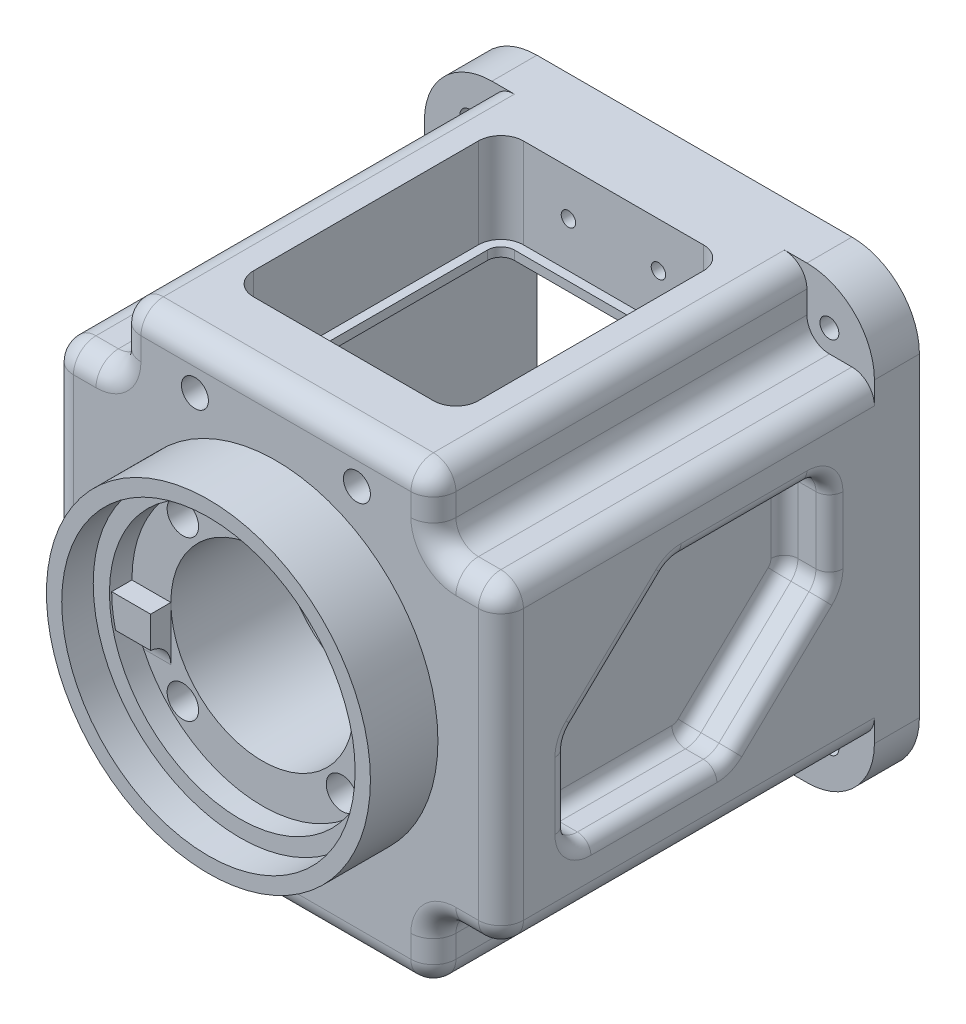
SolidWorks part; units mm, degrees
ref_plane "前视基准面" through (0, 0, 0) normal (0, 0, 1) x (1, 0, 0)
ref_plane "上视基准面" through (0, 0, 0) normal (0, 1, 0) x (1, 0, 0)
ref_plane "右视基准面" through (0, 0, 0) normal (1, 0, 0) x (0, 0, -1)
sketch "草图1" plane through (0, 0, 0) normal (0, 0, 1) x (1, 0, 0)
  line L1 (-50, 50) -> (50, 50)
  line L2 (-50, 50) -> (-50, -50)
  line L3 (-50, -50) -> (50, -50)
  line L4 (50, 50) -> (50, -50)
  line L5 (0, -50) -> (0, 50) construction
  line L6 (-50, 0) -> (50, 0) construction
  point P0 (0, 0)
  dimension "D1" = 100
  dimension "D2" = 100
extrude "凸台-拉伸1" add sketch "草图1" along normal blind 93
fillet "圆角1" radius 15 4 edges at (-50, -50, 46.5) (50, -50, 46.5) (50, 50, 46.5) (-50, 50, 46.5)
sketch "草图2" plane through (0, 0, 93) normal (0, 0, 1) x (1, 0, 0)
  line L0 (35, 50) -> (-35, 50) construction
  line L1 (-35, 50) -> (-50, 50)
  line L2 (-35, 50) -> (-35, 40)
  line L3 (-40, 35) -> (-50, 35)
  line L4 (-50, 50) -> (-50, 35)
  line L5 (-50, 35) -> (-50, -35) construction
  line L6 (50, 35) -> (40, 35)
  line L7 (50, 35) -> (50, 50)
  line L8 (50, 50) -> (35, 50)
  line L9 (35, 40) -> (35, 50)
  line L10 (35, -50) -> (35, -40)
  line L11 (35, -50) -> (50, -50)
  line L12 (50, -50) -> (50, -35)
  line L13 (40, -35) -> (50, -35)
  line L14 (-50, -35) -> (-40, -35)
  line L15 (-50, -35) -> (-50, -50)
  line L16 (-50, -50) -> (-35, -50)
  line L17 (-35, -40) -> (-35, -50)
  arc A0 (-35, 40) -> (-40, 35) centre (-40, 40) cw
  arc A1 (40, 35) -> (35, 40) centre (40, 40) cw
  arc A2 (35, -40) -> (40, -35) centre (40, -40) cw
  arc A3 (-40, -35) -> (-35, -40) centre (-40, -40) cw
  point P31 (0, 0)
  dimension "D3" = 5
  dimension "D1" = 15
  dimension "D2" = 15
  dimension "D4" = 4
extrude "切除-拉伸1" cut sketch "草图2" against normal offset from surface (83 mm away) 10 up to face at (0, 0, 0)
sketch "草图3" plane through (0, -50, 0) normal (0, -1, 0) x (1, 0, 0)
  line L1 (0, 46.5) -> (-87.2172, 46.5) construction
  line L4 (0, 46.5) -> (0, 0) construction
  line L5 (-35, 93) -> (35, 93) construction
  line L6 (-35, 0) -> (35, 0) construction
  circle A0 centre (0, 46.5) radius 25
  circle A1 centre (0, 46.5) radius 15
  dimension "D1" = 50
  dimension "D2" = 30
extrude "切除-拉伸2" cut sketch "草图3" against normal blind 7
sketch "草图4" plane through (0, -43, 0) normal (0, -1, 0) x (1, 0, 0)
  circle A0 centre (0, 46.5) radius 16
  circle A1 centre (0, 46.5) radius 24
  dimension "D1" = 48
  dimension "D2" = 32
extrude "切除-拉伸3" cut sketch "草图4" against normal blind 3
chamfer "倒角1" distance 1 angle 45 2 edges at (0, -50, 31.5) (0, -50, 21.5)
sketch "草图5" plane through (0, 0, 93) normal (0, 0, 1) x (1, 0, 0)
  circle A0 centre (0, 0) radius 36
  dimension "D1" = 72
extrude "凸台-拉伸2" add sketch "草图5" along normal blind 15
sketch "草图6" plane through (0, 0, 108) normal (0, 0, 1) x (1, 0, 0)
  circle A0 centre (0, 0) radius 32.6
  dimension "D2" = 65.2
extrude "切除-拉伸4" cut sketch "草图6" against normal blind 7
sketch "草图7" plane through (0, 0, 101) normal (0, 0, 1) x (1, 0, 0)
  circle A0 centre (0, 0) radius 29
  dimension "D1" = 58
extrude "切除-拉伸5" cut sketch "草图7" against normal blind 5
sketch "草图8" plane through (0, 0, 96) normal (0, 0, 1) x (1, 0, 0)
  line L0 (0, 0) -> (-51.1806, 0) construction
  line L1 (-17.6777, 17.6777) -> (0, 0) construction
  circle A0 centre (0, 0) radius 20.35
  circle A1 centre (-17.6777, 17.6777) radius 2.1
  circle A2 centre (17.6777, 17.6777) radius 2.1
  circle A3 centre (17.6777, -17.6777) radius 2.1
  circle A4 centre (-17.6777, -17.6777) radius 2.1
  point P15 (0, 0)
  dimension "D1" = 40.7
  dimension "D3" = 4.2
  dimension "D2" = 45
  dimension "D4" = 25
  dimension "D5" = 4
extrude "切除-拉伸6" cut sketch "草图8" against normal through all
sketch "草图9" plane through (0, 0, 96) normal (0, 0, 1) x (1, 0, 0)
  circle A0 centre (-17.6777, 17.6777) radius 3.5
  circle A1 centre (17.6777, 17.6777) radius 3.5
  circle A2 centre (-17.6777, -17.6777) radius 3.5
  circle A3 centre (17.6777, -17.6777) radius 3.5
  dimension "D1" = 7
extrude "切除-拉伸7" cut sketch "草图9" against normal blind 8
sketch "草图10" plane through (0, 0, 96) normal (0, 0, 1) x (1, 0, 0)
  line L1 (-20.35, 0) -> (-29.35, 0)
  line L2 (-20.35, 0) -> (-20.35, -7)
  line L3 (-20.35, -7) -> (-29.35, -7)
  line L4 (-29.35, 0) -> (-29.35, -7)
  circle A0 centre (0, 0) radius 20.35 construction
  dimension "D1" = 7
  dimension "D2" = 9
extrude "凸台-拉伸4" add sketch "草图10" along normal blind 4.5
fillet "圆角2" radius 5 1 edges at (-24.2462, -7, 96)
sketch "草图11" plane through (0, 0, 0) normal (0, 0, -1) x (-1, 0, 0)
  line L0 (35, -50) -> (-35, -50) construction
  line L1 (-25, 28) -> (25, 28)
  line L2 (-35, 18) -> (-35, -27)
  line L3 (-25, -37) -> (25, -37)
  line L4 (35, 18) -> (35, -27)
  line L5 (0, -37) -> (0, 28) construction
  line L6 (-35, -4.5) -> (35, -4.5) construction
  arc A0 (25, 28) -> (35, 18) centre (25, 18) cw
  arc A1 (-25, 28) -> (-35, 18) centre (-25, 18) ccw
  arc A2 (-35, -27) -> (-25, -37) centre (-25, -27) ccw
  arc A3 (25, -37) -> (35, -27) centre (25, -27) ccw
  point P0 (0, 0)
  point P6 (35, 28)
  point P10 (-35, 28)
  point P13 (-35, -37)
  dimension "D3" = 10
  dimension "D1" = 65
  dimension "D2" = 70
  dimension "D4" = 13
extrude "切除-拉伸8" cut sketch "草图11" against normal blind 88
sketch "草图12" plane through (0, 0, 88) normal (0, 0, -1) x (-1, 0, 0)
  line L1 (-22.5, 22.5) -> (22.5, 22.5)
  line L2 (-22.5, 22.5) -> (-22.5, -22.5)
  line L3 (-22.5, -22.5) -> (22.5, -22.5)
  line L4 (22.5, 22.5) -> (22.5, -22.5)
  line L5 (0, -22.5) -> (0, 22.5) construction
  line L6 (-22.5, 0) -> (22.5, 0) construction
  circle A3 centre (0, 0) radius 20.35 construction
  circle A8 centre (0, 0) radius 20.35
  circle A10 centre (-17.6777, 17.6777) radius 2.1
  circle A11 centre (17.6777, 17.6777) radius 2.1
  circle A12 centre (17.6777, -17.6777) radius 2.1
  circle A13 centre (-17.6777, -17.6777) radius 2.1
  point P0 (0, 0)
  point P18 (0, 0)
  dimension "D3" = 4.2
  dimension "D1" = 45
  dimension "D2" = 45
  dimension "D4" = 4
fillet "圆角3" radius 5 24 edges at (-45, -35, 93) (-36.4645, -36.4645, 93) (-35, -45, 93) (0, -50, 93) (36.4645, -36.4645, 93) (35, -45, 93) (45, -35, 93) (50, 0, 93) (45, 35, 93) (36.4645, 36.4645, 93) (35, 45, 93) (0, 50, 93) (-35, 45, 93) (-36.4645, 36.4645, 93) (-45, 35, 93) (-50, 0, 93) (35, 50, 51.5) (50, 35, 51.5) (50, -35, 51.5) (35, -50, 51.5) (-35, -50, 51.5) (-50, -35, 51.5) (-50, 35, 51.5) (-35, 50, 51.5)
sketch "草图13" plane through (0, 50, 0) normal (0, 1, 0) x (1, 0, 0)
  line L0 (35, 0) -> (-35, 0) construction
  line L1 (-20, -20) -> (20, -20)
  line L2 (-23, -23) -> (-23, -73)
  line L3 (-20, -76) -> (20, -76)
  line L4 (23, -23) -> (23, -73)
  line L5 (0, -76) -> (0, -20) construction
  line L6 (-23, -48) -> (23, -48) construction
  arc A0 (20, -20) -> (23, -23) centre (20, -23) cw
  arc A1 (-20, -20) -> (-23, -23) centre (-20, -23) ccw
  arc A2 (-23, -73) -> (-20, -76) centre (-20, -73) ccw
  arc A3 (20, -76) -> (23, -73) centre (20, -73) ccw
  point P0 (0, -48)
  point P8 (23, -20)
  point P12 (-23, -20)
  point P15 (-23, -76)
  dimension "D4" = 3
  dimension "D1" = 56
  dimension "D2" = 46
  dimension "D3" = 20
extrude "切除-拉伸10" cut sketch "草图13" against normal up to next
sketch "草图14" plane through (0, 50, 0) normal (0, 1, 0) x (1, 0, 0)
  line L0 (30, -88) -> (30, -10) construction
  line L1 (-20, -18) -> (20, -18)
  line L2 (-25, -23) -> (-25, -73)
  line L3 (-20, -78) -> (20, -78)
  line L4 (25, -23) -> (25, -73)
  line L5 (0, -78) -> (0, -18) construction
  line L6 (-25, -48) -> (25, -48) construction
  line L7 (-30, -10) -> (-30, -88) construction
  line L8 (20, -20) -> (-20, -20) construction
  line L9 (-20, -76) -> (20, -76) construction
  arc A0 (20, -78) -> (25, -73) centre (20, -73) ccw
  arc A1 (-25, -73) -> (-20, -78) centre (-20, -73) ccw
  arc A2 (20, -18) -> (25, -23) centre (20, -23) cw
  arc A3 (-20, -18) -> (-25, -23) centre (-20, -23) ccw
  point P0 (0, -48)
  dimension "D2" = 5
  dimension "D1" = 60
  dimension "D3" = 50
extrude "切除-拉伸11" cut sketch "草图14" against normal blind 20
sketch "草图15" plane through (-50, 0, 0) normal (-1, 0, 0) x (0, 0, 1)
  line L0 (78, -22) -> (78, 0)
  line L1 (78, 0) -> (55, 22)
  line L2 (55, 22) -> (20, 22)
  line L3 (20, 22) -> (20, 0)
  line L4 (20, 0) -> (43, -22)
  line L5 (43, -22) -> (78, -22)
  line L6 (0, 35) -> (0, -35) construction
  line L7 (93, 30) -> (93, -30) construction
  line L8 (78, 0) -> (20, 0) construction
  line L9 (88, 30) -> (10, 30) construction
  line L10 (10, -30) -> (88, -30) construction
  dimension "D1" = 20
  dimension "D2" = 35
  dimension "D3" = 15
  dimension "D4" = 22
extrude "切除-拉伸12" cut sketch "草图15" against normal blind 10
mirror "镜向1" about plane through (0, 0, 0) normal (1, 0, 0) of "切除-拉伸12"
fillet "圆角4" radius 5 12 edges at (-45, 22, 20) (-45, 0, 20) (-45, -22, 43) (-45, -22, 78) (-45, 0, 78) (-45, 22, 55) (45, 0, 78) (45, 22, 55) (45, 22, 20) (45, 0, 20) (45, -22, 43) (45, -22, 78)
fillet "圆角5" radius 3 48 edges at (-40, 21.6404, 54.8557) (-40, 11.045, 66.453) (-40, -0.1718, 77.5979) (-40, -20.5355, 76.5355) (-40, -22, 59.0031) (-40, -21.6404, 43.1443) (-40, -11.045, 31.547) (-40, 0.1718, 20.4021) (-40, 9.5682, 20) (-40, 20.5355, 21.4645) (-50, 21.6404, 54.8557) (-50, -0.1718, 77.5979) (-50, -9.5682, 78) (-50, -20.5355, 76.5355) (-50, -21.6404, 43.1443) (-50, 0.1718, 20.4021) (-50, 20.5355, 21.4645) (-50, 9.5682, 20) (-50, -11.045, 31.547) (-50, -22, 59.0031) (-40, -9.5682, 78) (-50, 11.045, 66.453) (-40, 22, 38.9969) (-50, 22, 38.9969) (40, -21.6404, 43.1443) (40, -11.045, 31.547) (40, 0.1718, 20.4021) (40, 9.5682, 20) (40, 20.5355, 21.4645) (40, 22, 38.9969) (40, 21.6404, 54.8557) (40, 11.045, 66.453) (40, -0.1718, 77.5979) (40, -9.5682, 78) (40, -20.5355, 76.5355) (50, -21.6404, 43.1443) (50, -11.045, 31.547) (50, 0.1718, 20.4021) (50, 9.5682, 20) (50, 20.5355, 21.4645) (50, 22, 38.9969) (50, 21.6404, 54.8557) (50, 11.045, 66.453) (50, -0.1718, 77.5979) (50, -9.5682, 78) (50, -20.5355, 76.5355) (40, -22, 59.0031) (50, -22, 59.0031)
sketch "草图16" plane through (0, 0, 0) normal (0, 0, -1) x (-1, 0, 0)
  line L0 (0, 0) -> (-72.8216, 0) construction
  line L1 (0, 0) -> (0, 55.6769) construction
  circle A0 centre (-40, 40) radius 2.1
  circle A1 centre (40, 40) radius 2.1
  circle A2 centre (40, -40) radius 2.1
  circle A3 centre (-40, -40) radius 2.1
  point P15 (0, 0)
  dimension "D3" = 4.2
  dimension "D1" = 40
  dimension "D2" = 40
  dimension "D4" = 4
extrude "切除-拉伸13" cut sketch "草图16" against normal through all
sketch "草图17" plane through (0, -40, 0) normal (0, -1, 0) x (1, 0, 0)
  line L0 (19, 52.5) -> (19, 40.5) construction
  line L3 (0, 0) -> (0, 66) construction
  line L4 (22.2, 52.5) -> (22.2, 40.5)
  line L7 (19, 46.5) -> (-28.2912, 46.5) construction
  line L8 (15.8, 52.5) -> (15.8, 40.5)
  arc A4 (22.2, 52.5) -> (15.8, 52.5) centre (19, 52.5) ccw
  arc A5 (15.8, 40.5) -> (22.2, 40.5) centre (19, 40.5) ccw
  circle A7 centre (0, 46.5) radius 8.4626 construction
  point P2 (19, 46.5)
  dimension "D3" = 3.2
  dimension "D1" = 19
  dimension "D2" = 12
extrude "切除-拉伸14" cut sketch "草图17" against normal up to next
sketch "草图18" plane through (0, 0, 0) normal (0, 0, -1) x (-1, 0, 0)
  line L0 (0, 0) -> (0, 55.6154) construction
  line L1 (-35, 50) -> (35, 50) construction
  circle A0 centre (-10, 40) radius 1.6
  circle A1 centre (10, 40) radius 1.6
  dimension "D3" = 3.2
  dimension "D1" = 10
  dimension "D2" = 10
extrude "切除-拉伸15" cut sketch "草图18" against normal up to next
sketch "草图19" plane through (0, 0, 0) normal (0, 0, -1) x (-1, 0, 0)
  circle A0 centre (-10, 40) radius 3
  circle A1 centre (10, 40) radius 3
  dimension "D1" = 6
extrude "切除-拉伸16" cut sketch "草图19" against normal offset from surface (10 mm away) 8 up to face at (8.4, 40, 18)
sketch "草图20" plane through (0, 0, 78) normal (0, 0, -1) x (-1, 0, 0)
  line L0 (0, 0) -> (0, 55.0796) construction
  line L1 (20, 50) -> (-20, 50) construction
  circle A0 centre (-18, 40) radius 1.6
  circle A1 centre (18, 40) radius 1.6
  dimension "D1" = 3.2
  dimension "D2" = 36
  dimension "D3" = 10
extrude "切除-拉伸17" cut sketch "草图20" against normal through all
sketch "草图21" plane through (0, 0, 93) normal (0, 0, 1) x (1, 0, 0)
  circle A0 centre (-18, 40) radius 3
  circle A1 centre (18, 40) radius 3
  dimension "D1" = 6
extrude "切除-拉伸18" cut sketch "草图21" against normal blind 8
extrude "凸台-拉伸5" add sketch "草图12" along normal blind 17
sketch "草图22" plane through (0, 0, 71) normal (0, 0, -1) x (-1, 0, 0)
  circle A0 centre (-17.6777, -17.6777) radius 7
  circle A1 centre (17.6777, 17.6777) radius 7
  dimension "D1" = 14
extrude "切除-拉伸19" cut sketch "草图22" against normal blind 5
